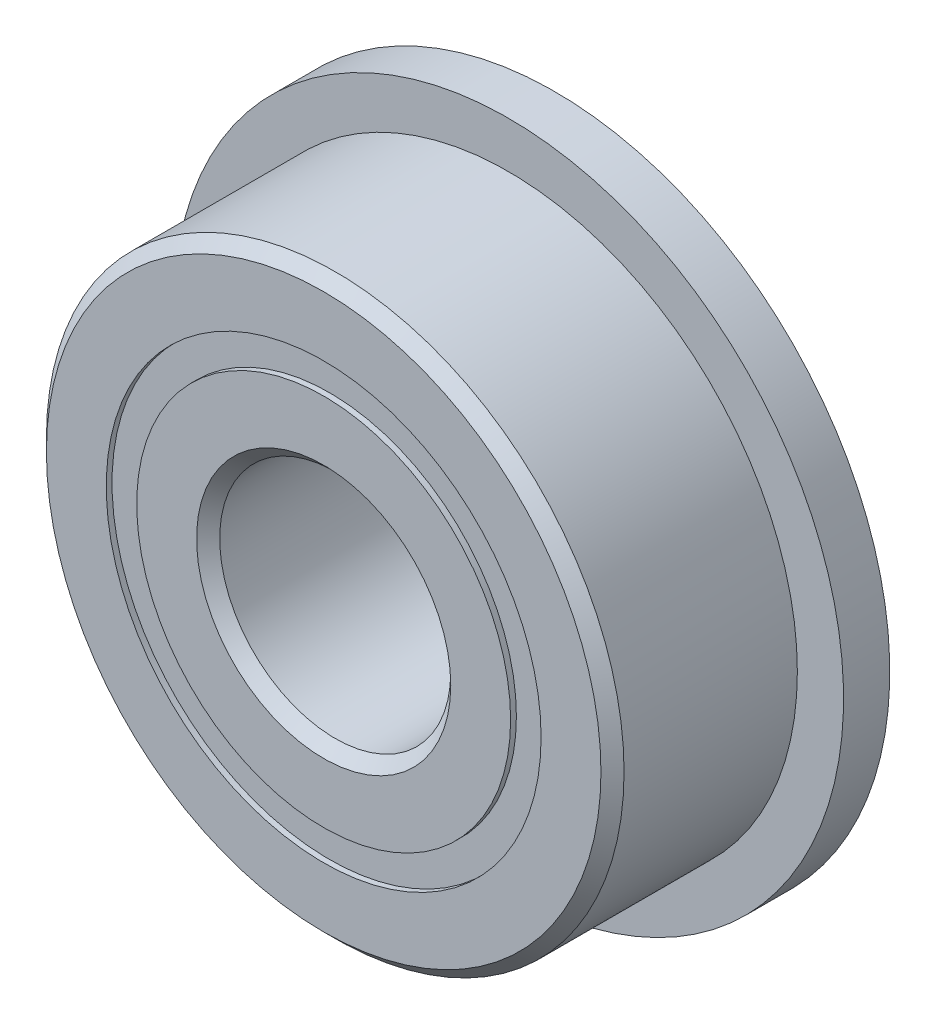
SolidWorks part; units mm, degrees
ref_plane "Front Plane" through (0, 0, 0) normal (0, 0, 1) x (1, 0, 0)
ref_plane "Top Plane" through (0, 0, 0) normal (0, 1, 0) x (1, 0, 0)
ref_plane "Right Plane" through (0, 0, 0) normal (1, 0, 0) x (0, 0, -1)
sketch "Sketch1" plane through (0, 0, 0) normal (1, 0, 0) x (0, 0, -1)
  line L0 (-2, 0) -> (2, 0) construction
  line L1 (0, 5) -> (0, -5) construction
  line L2 (1.8, 5) -> (-1.8, 5)
  line L3 (-1.8, 5) -> (-2, 4.8)
  line L4 (-2, 4.8) -> (-2, 3.7637)
  line L5 (-2, 3.7637) -> (-0.8889, 3.7637)
  line L6 (2, 3.7637) -> (0.8889, 3.7637)
  line L7 (2, 4.8) -> (2, 3.7637)
  line L8 (1.8, 5) -> (2, 4.8)
  line L9 (0, 5) -> (0, 3.5) construction
  line L10 (0, 3.5) -> (0, 2) construction
  arc A0 (-0.8889, 3.7637) -> (0.8889, 3.7637) centre (0, 3.5) cw
  point P14 (0, 2)
  dimension "D3" = 1.7778
  dimension "D1" = 45
  dimension "Width" = 4
  dimension "OD" = 10
  dimension "D2" = 0.2
  dimension "Shaft Dia" = 4
  dimension "D4" = 0.2637
revolve "Revolve1" add sketch "Sketch1" angle 360 about L0
sketch "Sketch3" plane through (0, 0, 0) normal (1, 0, 0) x (0, 0, -1)
  line L0 (-2, 3.2363) -> (-0.8889, 3.2363)
  line L1 (0, 5) -> (0, -5) construction
  line L2 (-2, 4.8) -> (-2, 3.7637) construction
  line L3 (-2, 3.2363) -> (-2, 2.2)
  line L4 (-1.8, 5) -> (-2, 4.8) construction
  line L5 (-2, 2.2) -> (-1.8, 2)
  line L6 (-1.8, 2) -> (1.8, 2)
  line L7 (1.8, 5) -> (1.8, -5) construction
  line L8 (1.8, 2) -> (2, 2.2)
  line L9 (2, -4.8) -> (2, 4.8) construction
  line L10 (2, 2.2) -> (2, 3.2363)
  line L11 (2, 3.2363) -> (0.8889, 3.2363)
  line L13 (1.8, 5) -> (2, 4.8) construction
  arc A0 (0.8889, 3.7637) -> (-0.8889, 3.7637) centre (0, 3.5) ccw construction
  arc A1 (0.8889, 3.2363) -> (-0.8889, 3.2363) centre (0, 3.5) cw
revolve "Revolve3" add sketch "Sketch3" angle 360 about L0
sketch "Sketch4" plane through (0, 0, 0) normal (1, 0, 0) x (0, 0, -1)
  line L0 (-0.9272, 3.5) -> (0.9272, 3.5)
  arc A2 (-0.9272, 3.5) -> (0.9272, 3.5) centre (0, 3.5) cw
  arc A3 (0.8889, 3.7637) -> (-0.8889, 3.7637) centre (0, 3.5) ccw construction
revolve "Revolve4" add sketch "Sketch4" angle 360 about L0
ref_axis "Axis1" through (0, 0, -2) along (0, 0, 1)
pattern_circular "CirPattern1" count 12 every 30 about axis through (0, 0, -2) along (0, 0, 1) of bodies 104
sketch "Sketch5" plane through (0, 0, 0) normal (1, 0, 0) x (0, 0, -1)
  line L0 (-2, 3.7637) -> (-0.8889, 3.7637) construction
  line L1 (-1.9, 3.7637) -> (-0.9272, 3.7637)
  line L2 (-1.9, 3.7637) -> (-1.9, 3.2363)
  line L3 (-1.9, 3.2363) -> (-0.9272, 3.2363)
  line L4 (-0.9272, 3.7637) -> (-0.9272, 3.2363)
  line L5 (-2, 3.2363) -> (-0.8889, 3.2363) construction
  line L6 (2, 3.7637) -> (0.8889, 3.7637) construction
  line L7 (1.9, 3.7637) -> (0.9272, 3.7637)
  line L8 (1.9, 3.7637) -> (1.9, 3.2363)
  line L9 (1.9, 3.2363) -> (0.9272, 3.2363)
  line L10 (0.9272, 3.7637) -> (0.9272, 3.2363)
  line L11 (2, 3.2363) -> (0.8889, 3.2363) construction
  line L12 (-1.8, 5) -> (-2, 4.8) construction
  point P18 (-1.9, 4.9)
revolve "Revolve5" add sketch "Sketch5" angle 360 about L0
sketch "Sketch6" plane through (0, 0, 0) normal (1, 0, 0) x (0, 0, -1)
  line L0 (2, 0) -> (-2, 0) construction
  line L1 (2, 3.7637) -> (1.2, 3.7637)
  line L2 (2, 3.7637) -> (2, 5.8)
  line L3 (2, 5.8) -> (1.2, 5.8)
  line L4 (1.2, 3.7637) -> (1.2, 5.8)
  dimension "Th" = 0.8
  dimension "Flange OD" = 11.6
revolve "Revolve6" add sketch "Sketch6" angle 360 about L0
equation "\"D2@Sketch1\" = \"Width@Sketch1\"*.05"
equation "\"D3@Sketch1\" = \"Width@Sketch1\"/2.25"
equation "\"D4@Sketch1\" = (((\"OD@Sketch1\"-\"Width@Sketch1\")/2)/3.25)/3.5"
equation "\"D2@CirPattern1\" = 360/\"Balls@CirPattern1\""
